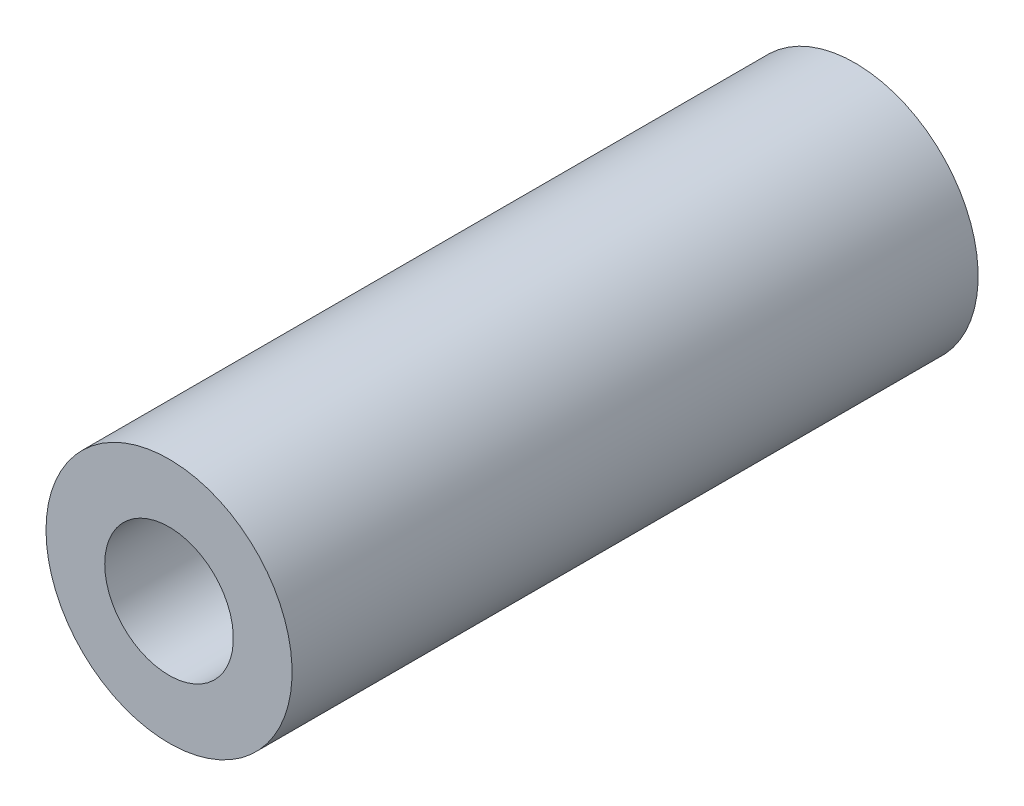
SolidWorks part; units mm, degrees
material "6061-T6 (SS)"
ref_plane "Front Plane" through (0, 0, 0) normal (0, 0, 1) x (1, 0, 0)
ref_plane "Top Plane" through (0, 0, 0) normal (0, 1, 0) x (1, 0, 0)
ref_plane "Right Plane" through (0, 0, 0) normal (1, 0, 0) x (0, 0, -1)
sketch "Sketch1" plane through (0, 0, 0) normal (0, 0, 1) x (1, 0, 0)
  circle A0 centre (0, 0) radius 2.4892
  circle A1 centre (0, 0) radius 4.7625
  dimension "D1" = 4.9784
  dimension "D2" = 9.525
extrude "Boss-Extrude1" add sketch "Sketch1" along normal blind 26.5557
